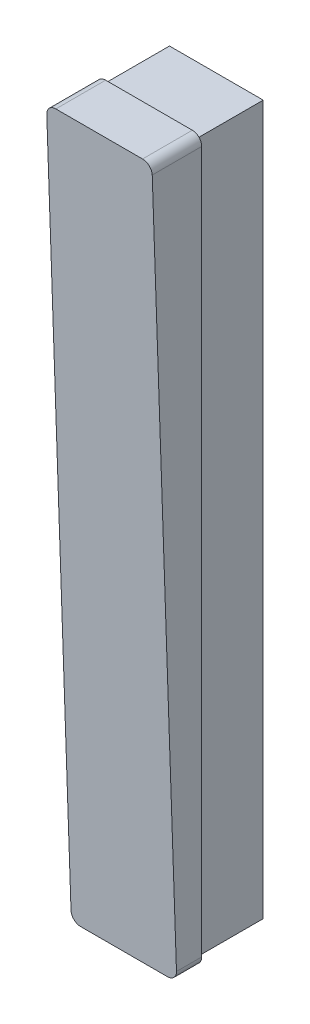
SolidWorks part; units mm, degrees
ref_plane "Front Plane" through (0, 0, 0) normal (0, 0, 1) x (1, 0, 0)
ref_plane "Top Plane" through (0, 0, 0) normal (0, 1, 0) x (1, 0, 0)
ref_plane "Right Plane" through (0, 0, 0) normal (1, 0, 0) x (0, 0, -1)
ref_plane "Plane1" through (-28.575, 0, 0) normal (-1, 0, 0) x (0, -1, 0)
sketch "Sketch1" plane through (-28.575, 0, 0) normal (-1, 0, 0) x (0, -1, 0)
  line L0 (195.2625, 13.4937) -> (-195.2625, 26.9875)
  line L1 (-195.2625, 26.9875) -> (-195.2625, 0)
  line L2 (-195.2625, 0) -> (195.2625, 0)
  line L3 (195.2625, 0) -> (195.2625, 13.4937)
  point P4 (0, 0)
  dimension "D1" = 390.525
  dimension "D2" = 26.9875
  dimension "D3" = 13.4937
extrude "Boss-Extrude1" add sketch "Sketch1" against normal blind 57.15
sketch "Sketch15" plane through (0, 0, 0) normal (0, 0, -1) x (-1, 0, 0)
  line L0 (25.4, -192.0875) -> (-25.4, -192.0875)
  line L1 (-25.4, -192.0875) -> (-25.4, 192.0875)
  line L2 (-25.4, 192.0875) -> (25.4, 192.0875)
  line L3 (25.4, 192.0875) -> (25.4, -192.0875)
  line L5 (-25.4, 192.0875) -> (25.4, -192.0875) construction
  line L6 (-25.4, -192.0875) -> (25.4, 192.0875) construction
  dimension "D1" = 384.175
  dimension "D2" = 50.8
extrude "Boss-Extrude7" add sketch "Sketch15" along normal blind 36.5125
hole_wizard "M8 Clearance Hole1" positions "Sketch23" profile "Sketch22" hole size "M8" standard "ANSI Metric"
sketch "Sketch23" plane through (0, 0, -36.5125) normal (0, 0, -1) x (-1, 0, 0)
  line L0 (25.4, 192.0875) -> (-25.4, 192.0875) construction
  line L1 (0, -122.2375) -> (0, 100.0125) construction
  line L3 (25.4, -192.0875) -> (25.4, 192.0875) construction
  line L4 (-25.4, 192.0875) -> (-25.4, -192.0875) construction
  point P0 (0, 100.0125)
  point P1 (0, -122.2375)
  dimension "D1" = 222.25
  dimension "D2" = 92.075
sketch "Sketch22" plane through (0, 100.0125, -36.5125) normal (1, 0, 0) x (0, 1, 0)
  line L0 (0, 0) -> (0, 26.8921)
  line L1 (0, 26.8921) -> (4.2164, 24.3586)
  line L2 (4.2164, 24.3586) -> (4.2164, 0)
  line L5 (4.2164, 0) -> (0, 0)
  line L10 (0, 26.8921) -> (-4.2164, 24.3586) construction
  line L11 (0, -6.35) -> (0, 107.95) construction
  dimension "Hole Dia." = 8.4328
  dimension "Hole Depth" = 24.3586
  dimension "Drill Angle" = 118
sketch3d "3DSketch1"
  line L0 (0, 144.4625, -36.5125) -> (0, -166.6875, -36.5125) construction
  line L1 (-25.4, 192.0875, -36.5125) -> (25.4, 192.0875, -36.5125) construction
  line L2 (25.4, -192.0875, -36.5125) -> (-25.4, -192.0875, -36.5125) construction
  point P0 (0, 144.4625, -36.5125)
  point P1 (0, -166.6875, -36.5125)
  dimension "D1" = 47.625
  dimension "D2" = 25.4
fillet "Fillet1" radius 5.08 4 edges at (-28.575, 195.2625, 13.4937) (-28.575, -195.2625, 6.7469) (28.575, 195.2625, 13.4937) (28.575, -195.2625, 6.7469) tangent propagation no
hole_wizard "3/4 NPT Tapped Hole1" positions "Sketch26" profile "Sketch27" size "3/4" standard "ANSI Inch"
sketch "Sketch26" plane through (0, 0, -36.5125) normal (0, 0, -1) x (-1, 0, 0)
  point P0 (0, 144.4625)
  point P3 (0, -166.6875)
sketch "Sketch27" plane through (0, 144.4625, -36.5125) normal (1, 0, 0) x (0, 1, 0)
  line L0 (0, 0) -> (0, 30.0276)
  line L1 (11.5062, 23.114) -> (0, 30.0276)
  line L2 (-11.5062, 23.114) -> (0, 30.0276) construction
  line L3 (11.5062, 23.114) -> (11.5062, 14.0462)
  line L4 (11.5062, 14.0462) -> (12.9142, 14.0462)
  line L5 (12.9142, 14.0462) -> (13.3348, 0)
  line L6 (-12.9142, 14.0462) -> (-13.3348, 0) construction
  line L7 (13.3348, 0) -> (0, 0)
  line L8 (0, -6.35) -> (0, 107.95) construction
  line L11 (-11.5062, 14.0462) -> (-12.9142, 14.0462) construction
  dimension "Tap Drill Dia." = 23.0124
  dimension "Tap Drill Depth" = 23.114
  dimension "Thread Dia." = 26.6695
  dimension "Thread Angle" = 3.43
  dimension "Thread Depth" = 14.0462
  dimension "Drill Angle" = 118
